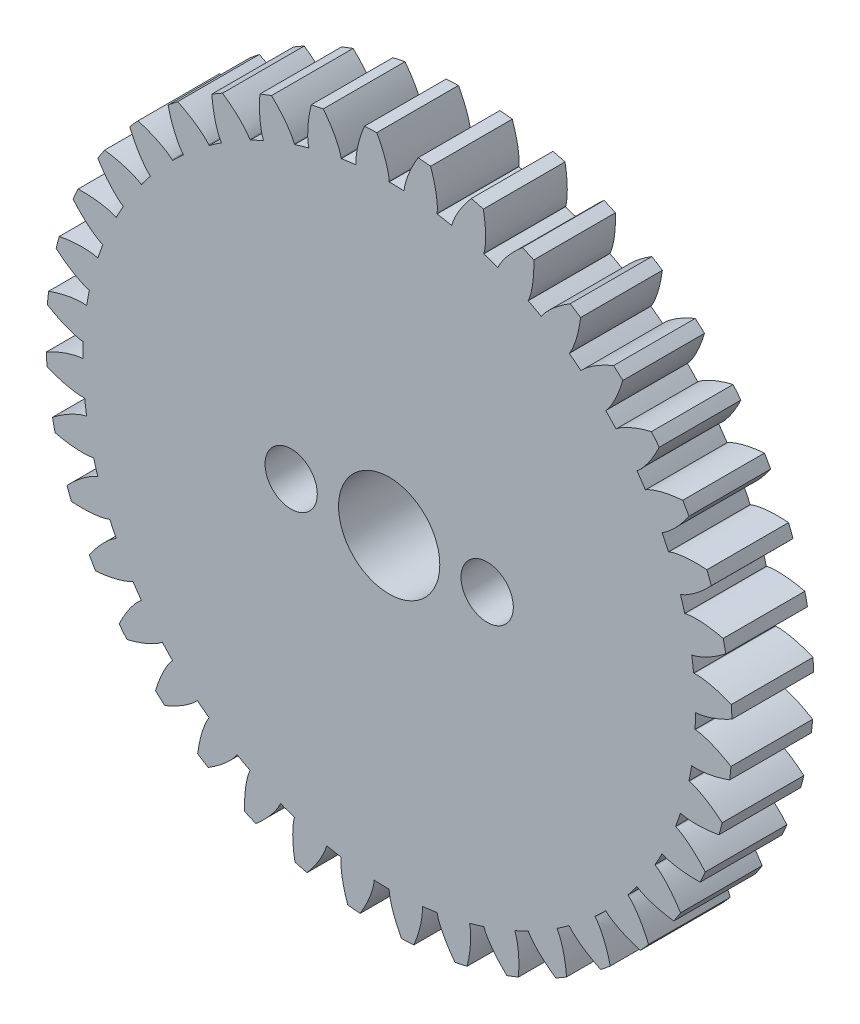
SolidWorks part; units mm, degrees
ref_plane "正面" through (0, 0, 0) normal (0, 0, 1) x (1, 0, 0)
ref_plane "平面" through (0, 0, 0) normal (0, 1, 0) x (1, 0, 0)
ref_plane "右側面" through (0, 0, 0) normal (1, 0, 0) x (0, 0, -1)
sketch "ｽｹｯﾁ1" plane through (0, 0, 0) normal (0, 0, 1) x (1, 0, 0)
  line L0 (18.7939, 0) -> (0, 0)
  line L1 (0, 0) -> (100, -2.4374)
  circle A0 centre (0, 0) radius 18.7939
  circle A1 centre (0, 0) radius 20
  circle A2 centre (0, 0) radius 21
  circle A3 centre (0, 0) radius 18.75
  spline S0 degree 4 poles (18.7939, 0) (18.8518, 0.0025) (19.0136, 0.0172) (19.3184, 0.076) (19.8033, 0.2143) (20.4111, 0.4551) (21.161, 0.8336) (21.9932, 1.3596) (22.8508, 2.0184) (23.9236, 3.0046) (24.8881, 4.0989) (25.7817, 5.3228) (26.7153, 6.8683) (27.52, 8.4858) (28.276, 10.4439) (28.8973, 12.6918) (29.3098, 14.9869) (29.5231, 17.3086) (29.5469, 19.6397) (29.3903, 21.9653) (29.0623, 24.2731) (28.6333, 26.2665) (28.2077, 27.811) (27.8554, 28.9203) (27.6195, 29.6101) (27.4235, 30.1553) (27.2151, 30.705) (27.0047, 31.2367) (26.7939, 31.7429) (26.6172, 32.1541) (26.4095, 32.6188) (26.2717, 32.919) (26.0452, 33.4004) (25.8614, 33.7739) (25.6369, 34.2226) (25.4285, 34.6221) (25.2021, 35.0475) (24.979, 35.4517) (24.8034, 35.7631) (24.6869, 35.9649) (24.6278, 36.0665) knots 0 0 0 0 0 0.005604 0.015718 0.02996 0.048734 0.068727 0.096889 0.125051 0.153212 0.209535 0.237696 0.271429 0.327752 0.384075 0.440398 0.496721 0.553044 0.609367 0.66569 0.722013 0.778336 0.806497 0.820578 0.834659 0.84874 0.86282 0.876901 0.890982 0.900036 0.909091 0.920455 0.931818 0.943182 0.954545 0.965909 0.977273 0.988636 1 1 1 1 1 construction
  spline S1 degree 4 poles (18.7939, 0) (18.8518, 0.0025) (19.0136, 0.0172) (19.3184, 0.076) (19.8033, 0.2143) (20.4111, 0.4551) (21.161, 0.8336) (21.9932, 1.3596) (22.8508, 2.0184) (23.9236, 3.0046) (24.8881, 4.0989) (25.7817, 5.3228) (26.7153, 6.8683) (27.52, 8.4858) (28.276, 10.4439) (28.8973, 12.6918) (29.3098, 14.9869) (29.5231, 17.3086) (29.5469, 19.6397) (29.3903, 21.9653) (29.0623, 24.2731) (28.6333, 26.2665) (28.2077, 27.811) (27.8554, 28.9203) (27.6195, 29.6101) (27.4235, 30.1553) (27.2151, 30.705) (27.0047, 31.2367) (26.7939, 31.7429) (26.6172, 32.1541) (26.4637, 32.4975) (26.3928, 32.6538) (26.3574, 32.7312) knots 0 0 0 0 0 0.005604 0.015718 0.02996 0.048734 0.068727 0.096889 0.125051 0.153212 0.209535 0.237696 0.271429 0.327752 0.384075 0.440398 0.496721 0.553044 0.609367 0.66569 0.722013 0.778336 0.806497 0.820578 0.834659 0.84874 0.86282 0.876901 0.890982 0.900036 0.909091 0.909091 0.909091 0.909091 0.909091
  point P11 (19.9978, 0.298)
  point P12 (19.9941, -0.4873)
  dimension "D1" = 40
  dimension "D2" = 37.5877
  dimension "D3" = 42
  dimension "D4" = 37.5
  dimension "D6" = 100
  dimension "D5" = 0.7854
extrude "ﾎﾞｽ - 押し出し1" add sketch "ｽｹｯﾁ1" along normal blind 5 contours A2
extrude "ｶｯﾄ - 押し出し1" cut sketch "ｽｹｯﾁ1<4>" along normal blind 5 contours S1 A1 L1 A2 | S1 A0 L1 A1 | A3 L1 A0 L0 region at (18.7701, -0.2287, 0) region at (19.4523, -0.1706, 0) region at (20.5375, 0.0163, 0)
sketch "ｽｹｯﾁ1<4>" plane through (0, 0, 0) normal (0, 0, 1) x (1, 0, 0) same geometry as "ｽｹｯﾁ1"
mirror "ﾐﾗｰ1" about plane through (0, 0, 5) normal (0.0244, 0.9997, 0) of "ｶｯﾄ - 押し出し1"
pattern_circular "円形ﾊﾟﾀｰﾝ10" count 40 over 360 about axis through (0, 0, 5) along (0, 0, -1) of "ﾐﾗｰ1", "ｶｯﾄ - 押し出し1"
sketch "ｽｹｯﾁ2" plane through (0, 0, 5) normal (0, 0, 1) x (1, 0, 0)
  circle A0 centre (0, 0) radius 3.1
  dimension "D1" = 6.2
extrude "ｶｯﾄ - 押し出し2" cut sketch "ｽｹｯﾁ2" against normal blind 10
sketch "ｽｹｯﾁ3" plane through (0, 0, 0) normal (0, 0, -1) x (-1, 0, 0)
  line L1 (0, 2.75) -> (0, -2.75) construction
  circle A0 centre (-6, 0) radius 1.6
  circle A5 centre (6, 0) radius 1.6
  dimension "D1" = 3.2
  dimension "D2" = 6
extrude "ｶｯﾄ - 押し出し3" cut sketch "ｽｹｯﾁ3" against normal blind 5
equation "\"モジュール\"= 1"
equation "\"歯数\"= 40"
equation "\"圧力角\"= 20"
equation "\"歯幅\"= 5"
equation "\"基準円直径\"= \"歯数\" * \"モジュール\""
equation "\"基礎円直径\"= \"基準円直径\" * cos ( \"圧力角\" )"
equation "\"歯先円直径\"= \"基準円直径\" + \"モジュール\" * 2"
equation "\"歯底円直径\"= \"基準円直径\" - \"モジュール\" * 2.5"
equation "\"D1@ｽｹｯﾁ1\"=\"基準円直径\""
equation "\"D3@ｽｹｯﾁ1\"=\"歯先円直径\""
equation "\"D1@ﾎﾞｽ - 押し出し1\"=\"歯幅\""
equation "\"D1@円形ﾊﾟﾀｰﾝ10\"=\"歯数\""
equation "\"D4@ｽｹｯﾁ1\"=\"歯底円直径\""
equation "\"D5@ｽｹｯﾁ1\"=\"モジュール\"*pi/4"
equation "\"D2@ｽｹｯﾁ1\"=\"基礎円直径\""
equation "\"D1@ｶｯﾄ - 押し出し3\"=\"歯幅\""
